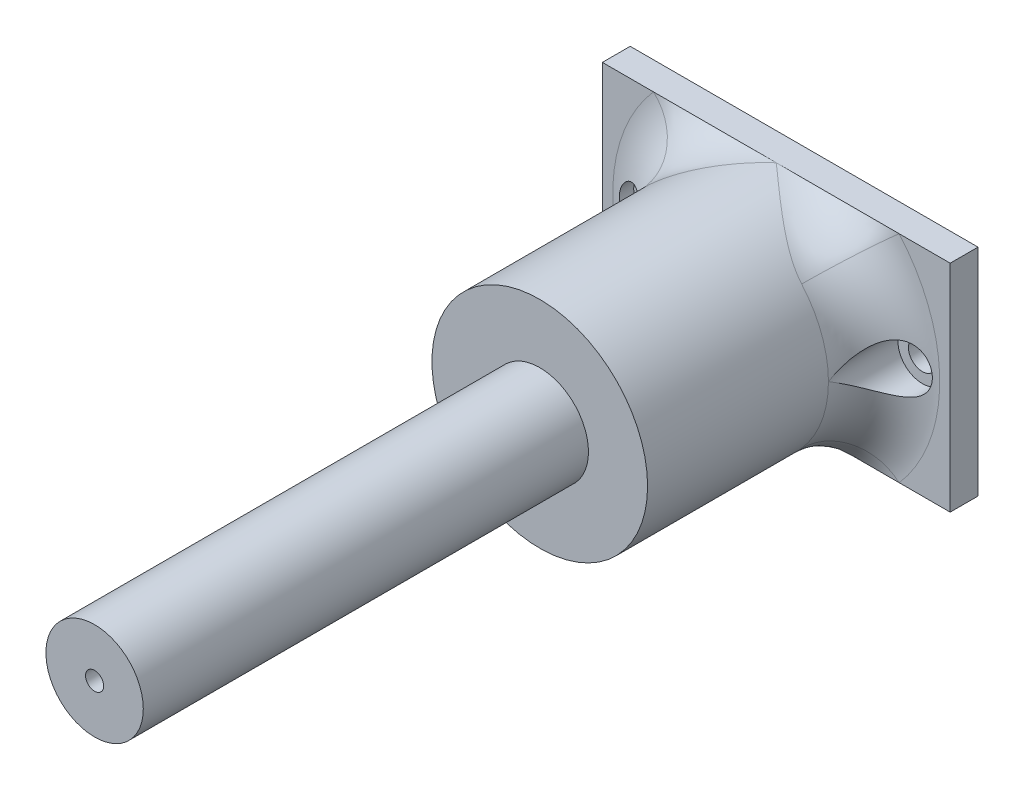
SolidWorks part; units mm, degrees
ref_plane "前视基准面" through (0, 0, 0) normal (0, 0, 1) x (1, 0, 0)
ref_plane "上视基准面" through (0, 0, 0) normal (0, 1, 0) x (1, 0, 0)
ref_plane "右视基准面" through (0, 0, 0) normal (1, 0, 0) x (0, 0, -1)
other "Configuration Table"
sketch "草图1" plane through (0, 0, 0) normal (0, 0, 1) x (1, 0, 0)
  line L1 (-12.5, -7.75) -> (12.5, -7.75)
  line L2 (-12.5, -7.75) -> (-12.5, 7.75)
  line L3 (-12.5, 7.75) -> (12.5, 7.75)
  line L4 (12.5, -7.75) -> (12.5, 7.75)
  line L5 (-12.5, -7.75) -> (12.5, 7.75) construction
  line L6 (-12.5, 7.75) -> (12.5, -7.75) construction
  line L7 (-7.75, 0) -> (7.75, 0) construction
  circle A1 centre (-9.5, 0) radius 1
  circle A2 centre (-9.5, 0) radius 1.75
  circle A3 centre (9.5, 0) radius 1.75
  circle A4 centre (9.5, 0) radius 1
  point P0 (0, 0)
  dimension "D1" = 19
  dimension "D2" = 2
  dimension "D3" = 3.5
  dimension "D4" = 3
extrude "凸台-拉伸1" add sketch "草图1" along normal blind 2 contours L3 L4 L1 L2 | A1 | A4
extrude "切除-拉伸3" cut sketch "草图1<4>" against normal blind 1 from surface contours A2 | A3 starting at face at (0, 0, 2)
sketch "草图1<4>" plane through (0, 0, 0) normal (0, 0, 1) x (1, 0, 0) same geometry as "草图1"
sketch "草图2" plane through (0, 0, 2) normal (0, 0, 1) x (1, 0, 0)
  circle A0 centre (0, 0) radius 7.75
  circle A1 centre (-9.5, 0) radius 1.75 construction
extrude "凸台-拉伸2" add sketch "草图2" along normal blind 17
fillet "圆角1" radius 4 4 edges at (5.4801, 5.4801, 2) (-5.4801, 5.4801, 2) (-5.4801, -5.4801, 2) (5.4801, -5.4801, 2)
sketch "草图3" plane through (0, 0, 19) normal (0, 0, 1) x (1, 0, 0)
  circle A0 centre (0, 0) radius 3.5
  dimension "D1" = 7
extrude "凸台-拉伸3" add sketch "草图3" along normal blind 32
sketch "草图4" plane through (0, 0, 51) normal (0, 0, 1) x (1, 0, 0)
  circle A0 centre (0, 0) radius 0.65
  dimension "D1" = 1.3
extrude "切除-拉伸7" cut sketch "草图4" against normal blind 2
